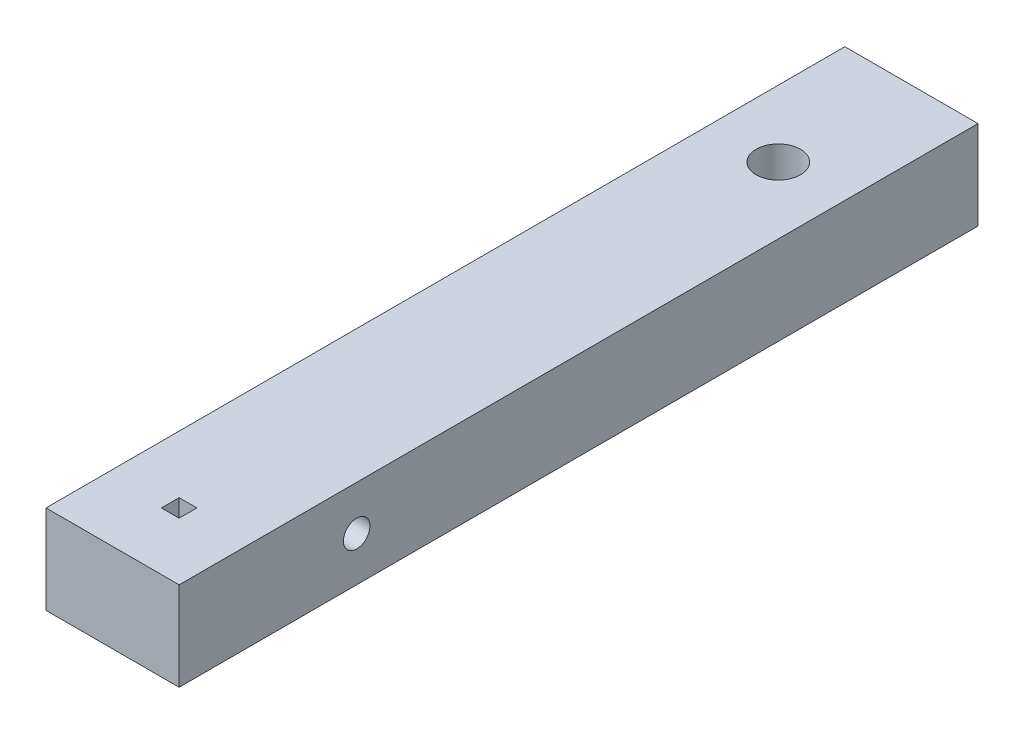
SolidWorks part; units mm, degrees
ref_plane "Plan de face" through (0, 0, 0) normal (0, 0, 1) x (1, 0, 0)
ref_plane "Plan de dessus" through (0, 0, 0) normal (0, 1, 0) x (1, 0, 0)
ref_plane "Plan de droite" through (0, 0, 0) normal (1, 0, 0) x (0, 0, -1)
sketch "Sketch1" plane through (0, 0, 0) normal (0, 1, 0) x (1, 0, 0)
  line L1 (7.5, -45) -> (-7.5, -45)
  line L2 (7.5, -45) -> (7.5, 45)
  line L3 (7.5, 45) -> (-7.5, 45)
  line L4 (-7.5, -45) -> (-7.5, 45)
  line L5 (7.5, -45) -> (-7.5, 45) construction
  line L6 (7.5, 45) -> (-7.5, -45) construction
  point P0 (0, 0)
  dimension "D1" = 90
  dimension "D2" = 15
extrude "Boss-Extrude1" add sketch "Sketch1" along normal blind 10
sketch "Sketch2" plane through (7.5, 0, 0) normal (1, 0, 0) x (0, 0, -1)
  line L0 (-45, 10) -> (-45, 0) construction
  line L1 (-45, 0) -> (45, 0) construction
  circle A0 centre (-25, 5) radius 1.5
  point P2 (-45, 5)
  dimension "D1" = 20
  dimension "D2" = 5
extrude "Cut-Extrude1" cut sketch "Sketch2" against normal through all
sketch "Sketch5" plane through (0, 0, 0) normal (0, -1, 0) x (1, 0, 0)
  line L0 (-7.5, -45) -> (-7.5, 45) construction
  line L1 (1, 36.5) -> (-1, 36.5)
  line L2 (1, 36.5) -> (1, 38.5)
  line L3 (1, 38.5) -> (-1, 38.5)
  line L4 (-1, 36.5) -> (-1, 38.5)
  line L5 (1, 36.5) -> (-1, 38.5) construction
  line L6 (1, 38.5) -> (-1, 36.5) construction
  line L7 (-7.5, 45) -> (7.5, 45) construction
  point P0 (0, 37.5)
  dimension "D1" = 2
  dimension "D2" = 2
  dimension "D3" = 7.5
  dimension "D4" = 7.5
extrude "Cut-Extrude4" cut sketch "Sketch5" against normal through all
sketch "Sketch6" plane through (0, 10, 0) normal (0, 1, 0) x (-1, 0, 0)
  line L0 (-7.5, -45) -> (7.5, -45) construction
  circle A0 centre (0, -30) radius 2.5
  point P2 (0, -45)
  dimension "D1" = 15
extrude "Cut-Extrude5" cut sketch "Sketch6" against normal through all
sketch "Sketch7" plane through (0, 0, -45) normal (0, 0, -1) x (-1, 0, 0)
  line L1 (1, 4) -> (-1, 4)
  line L2 (1, 4) -> (1, 6)
  line L3 (1, 6) -> (-1, 6)
  line L4 (-1, 4) -> (-1, 6)
  line L5 (1, 4) -> (-1, 6) construction
  line L6 (1, 6) -> (-1, 4) construction
  line L7 (-7.5, 10) -> (-7.5, 0) construction
  point P0 (0, 5)
  point P9 (0, 7.845)
  dimension "D1" = 2
  dimension "D2" = 2
  dimension "D3" = 7.5
  dimension "D4" = 5
extrude "Cut-Extrude6" cut sketch "Sketch7" against normal blind 15
